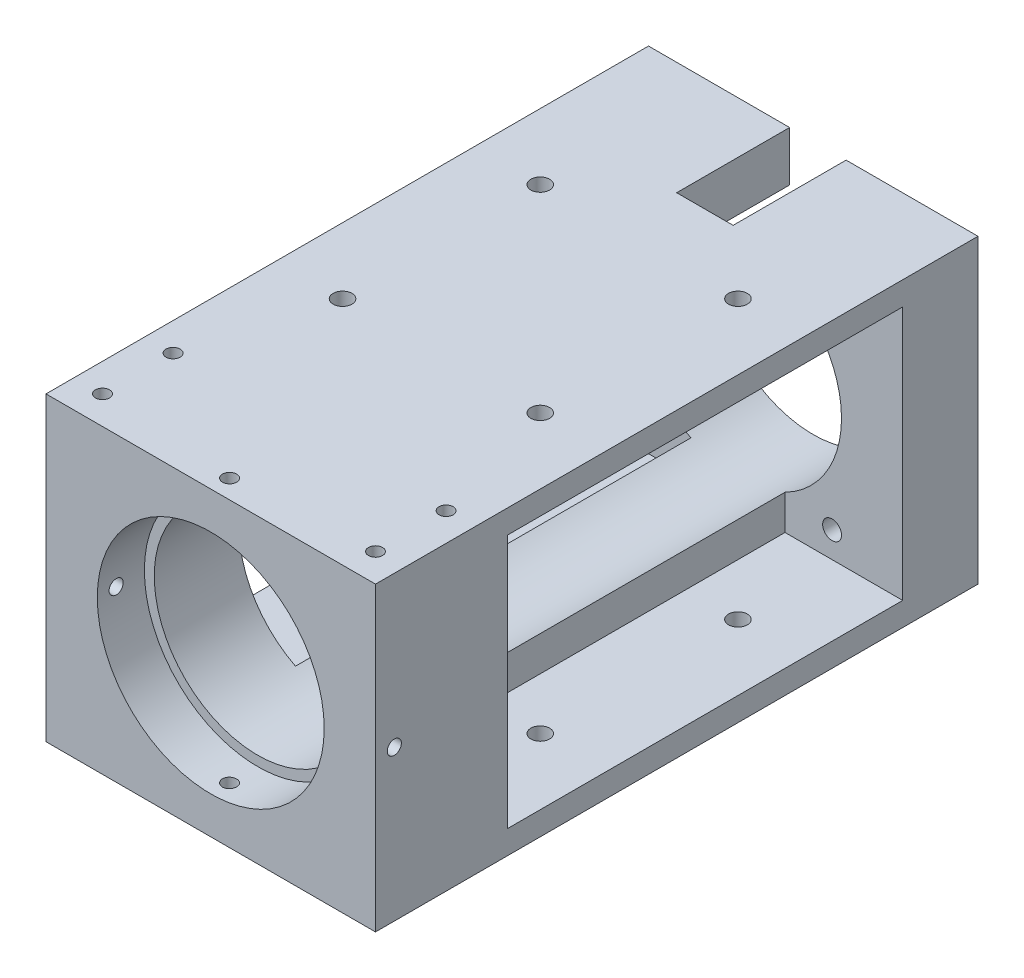
SolidWorks part; units mm, degrees
material "1060 合金"
ref_plane "前视基准面" through (0, 0, 0) normal (0, 0, 1) x (1, 0, 0)
ref_plane "上视基准面" through (0, 0, 0) normal (0, 1, 0) x (1, 0, 0)
ref_plane "右视基准面" through (0, 0, 0) normal (1, 0, 0) x (0, 0, -1)
sketch "草图1" plane through (0, 0, 0) normal (0, 0, 1) x (1, 0, 0)
  line L1 (-35, -32) -> (35, -32)
  line L2 (-35, -32) -> (-35, 32)
  line L3 (-35, 32) -> (35, 32)
  line L4 (35, -32) -> (35, 32)
  line L5 (-35, -32) -> (35, 32) construction
  line L6 (-35, 32) -> (35, -32) construction
  point P0 (0, 0)
  dimension "D1" = 70
  dimension "D2" = 64
extrude "凸台-拉伸1" add sketch "草图1" along normal mid plane 140
sketch "草图2" plane through (0, 0, 70) normal (0, 0, 1) x (1, 0, 0)
  circle A0 centre (0, 0) radius 24.1
  dimension "D1" = 48.2
extrude "切除-拉伸1" cut sketch "草图2" against normal blind 10
sketch "草图3" plane through (0, 32, 0) normal (0, 1, 0) x (1, 0, 0)
  line L0 (35, -70) -> (-35, -70) construction
  circle A0 centre (0, -66) radius 1.5
  point P5 (0, -70)
  dimension "D1" = 3
  dimension "D2" = 4
extrude "切除-拉伸2" cut sketch "草图3" against normal through all
sketch "草图4" plane through (35, 0, 0) normal (1, 0, 0) x (0, 0, -1)
  line L0 (-70, -32) -> (-70, 32) construction
  circle A0 centre (-66, 0) radius 1.5
  dimension "D1" = 3
  dimension "D2" = 4
extrude "切除-拉伸3" cut sketch "草图4" against normal through all
sketch "草图5" plane through (0, 0, 60) normal (0, 0, 1) x (1, 0, 0)
  circle A0 centre (0, 0) radius 22
  dimension "D1" = 44
extrude "切除-拉伸4" cut sketch "草图5" against normal through all
sketch "草图6" plane through (35, 0, 0) normal (1, 0, 0) x (0, 0, -1)
  line L1 (-42, -27) -> (42, -27)
  line L2 (-42, -27) -> (-42, 27)
  line L3 (-42, 27) -> (42, 27)
  line L4 (42, -27) -> (42, 27)
  line L5 (-42, -27) -> (42, 27) construction
  line L6 (-42, 27) -> (42, -27) construction
  point P0 (0, 0)
  dimension "D1" = 54
  dimension "D2" = 84
extrude "切除-拉伸5" cut sketch "草图6" against normal blind 25
mirror "镜向4" about plane through (0, 0, 0) normal (1, 0, 0) of "切除-拉伸5"
sketch "草图7" plane through (0, 32, 0) normal (0, 1, 0) x (1, 0, 0)
  line L0 (-21, 21) -> (21, 21) construction
  circle A0 centre (-21, 21) radius 2
  circle A1 centre (21, 21) radius 2
  point P4 (0, 21)
  dimension "D1" = 4
  dimension "D2" = 42
  dimension "D3" = 21
extrude "切除-拉伸6" cut sketch "草图7" against normal blind 20
sketch "草图8" plane through (0, 27, 0) normal (0, -1, 0) x (1, 0, 0)
  circle A1 centre (21, -21) radius 2 construction
  circle A2 centre (21, -21) radius 5.5
  circle A3 centre (21, -21) radius 5.5
  circle A4 centre (21, -21) radius 2
  circle M2 centre (21, -21) radius 2
  dimension "D1" = 3.5
extrude "切除-拉伸7" [suppressed] cut sketch "草图8" against normal blind 7 contours A3 M2
mirror "镜向1" [suppressed] about plane through (0, 0, 0) normal (1, 0, 0)
mirror "镜向2" about plane through (0, 0, 0) normal (0, 0, 1) of "镜向1", "切除-拉伸7", "切除-拉伸6"
sketch "草图9" plane through (0, 0, 0) normal (1, 0, 0) x (0, 0, -1)
  line L0 (-112.2479, 0) -> (108.0194, 0)
sketch "草图10" plane through (0, 0, -70) normal (0, 0, -1) x (-1, 0, 0)
  circle A0 centre (0, 0) radius 22 construction
  point P0 (0, -22)
sketch "草图11" plane through (0, 32, 0) normal (0, 1, 0) x (1, 0, 0)
  line L0 (-29, -64) -> (29, -64) construction
  line L1 (35, -70) -> (-35, -70) construction
  line L2 (-29, -49) -> (29, -49) construction
  circle A0 centre (-29, -64) radius 1.5
  circle A1 centre (29, -64) radius 1.5
  circle A2 centre (-29, -49) radius 1.5
  circle A3 centre (29, -49) radius 1.5
  point P4 (0, -64)
  point P7 (0, -70)
  point P12 (0, -49)
  dimension "D3" = 3
  dimension "D1" = 58
  dimension "D2" = 6
  dimension "D4" = 15
extrude "切除-拉伸8" cut sketch "草图11" against normal blind 10
sketch "草图12" plane through (35, 0, 0) normal (1, 0, 0) x (0, 0, -1)
  line L0 (-70, -32) -> (70, -32) construction
  line L1 (58, -32) -> (70, -32)
  line L2 (58, -32) -> (58, 32)
  line L3 (58, 32) -> (70, 32)
  line L4 (70, -32) -> (70, 32)
  line L5 (58, -32) -> (70, 32) construction
  line L6 (58, 32) -> (70, -32) construction
  point P0 (64, 0)
  point P6 (64, -32)
  dimension "D2" = 12
extrude "切除-拉伸9" cut sketch "草图12" against normal through all
sketch "草图13" plane through (0, 0, -58) normal (0, 0, -1) x (-1, 0, 0)
  line L0 (35, 32) -> (35, -32) construction
  line L1 (-35, -25) -> (35, -25)
  line L2 (-35, -25) -> (-35, 25)
  line L3 (-35, 25) -> (35, 25)
  line L4 (35, -25) -> (35, 25)
  line L5 (-35, -25) -> (35, 25) construction
  line L6 (-35, 25) -> (35, -25) construction
  circle A0 centre (0, 0) radius 22 construction
  circle A1 centre (0, 0) radius 22
  point P0 (0, 0)
  dimension "D1" = 50
extrude "凸台-拉伸2" add sketch "草图13" along normal blind 68
sketch "草图14" plane through (0, 25, 0) normal (0, 1, 0) x (1, 0, 0)
  line L0 (-35, 58) -> (35, 58) construction
  line L1 (20, 126) -> (-20, 126)
  line L2 (20, 126) -> (20, 58)
  line L3 (20, 58) -> (-20, 58)
  line L4 (-20, 126) -> (-20, 58)
  line L5 (20, 126) -> (-20, 58) construction
  line L6 (20, 58) -> (-20, 126) construction
  line L7 (-35, 126) -> (35, 126) construction
  point P0 (0, 92)
  point P7 (0, 126)
  point P12 (0, 58)
  dimension "D1" = 40
extrude "切除-拉伸10" cut sketch "草图14" against normal blind 20
fillet "圆角1" radius 3 2 edges at (-20, 9.1652, -92) (20, 9.1652, -92)
sketch "草图15" plane through (0, 25, 0) normal (0, 1, 0) x (1, 0, 0)
  line L0 (-30, 68) -> (-30, 116) construction
  line L1 (-35, 126) -> (-35, 58) construction
  line L2 (-35, 126) -> (-20, 126) construction
  circle A0 centre (-30, 68) radius 2
  circle A1 centre (-30, 116) radius 2
  dimension "D1" = 4
  dimension "D2" = 48
  dimension "D3" = 5
  dimension "D4" = 10
extrude "切除-拉伸11" cut sketch "草图15" against normal blind 10 contours A1 | A0 region at (-30, 25, -116)
mirror "镜向3" about plane through (0, 0, 0) normal (0, 1, 0) of "镜向1", "切除-拉伸7", "切除-拉伸6", "镜向2"
sketch "草图16" plane through (0, -32, 0) normal (0, -1, 0) x (1, 0, 0)
  line L0 (27, -48) -> (-27, -48) construction
  line L1 (-27, -48) -> (-27, 62) construction
  line L2 (-27, 62) -> (27, 62) construction
  line L3 (27, 62) -> (27, -48) construction
  line L4 (-35, 70) -> (35, 70) construction
  circle A0 centre (27, 62) radius 2
  circle A1 centre (-27, 62) radius 2
  circle A2 centre (27, -48) radius 2
  circle A3 centre (-27, -48) radius 2
  point P8 (0, 62)
  point P11 (0, 70)
  dimension "D1" = 4
  dimension "D2" = 110
  dimension "D3" = 54
  dimension "D4" = 8
extrude "切除-拉伸12" cut sketch "草图16" against normal blind 8
sketch "草图18" plane through (0, 0, -126) normal (0, 0, -1) x (-1, 0, 0)
  line L7 (20, 25) -> (20, 9.798)
  line L8 (-20, 9.798) -> (-20, 25)
  line L9 (-20, 25) -> (-35, 25)
  line L10 (-35, 25) -> (-35, -25)
  line L11 (-35, -25) -> (35, -25)
  line L12 (35, -25) -> (35, 25)
  line L13 (35, 25) -> (20, 25)
  line L14 (20, 25) -> (20, 9.798)
  line L15 (-20, 9.798) -> (-20, 25)
  line L16 (-20, 25) -> (-35, 25)
  line L17 (-35, 25) -> (-35, -25)
  line L18 (-35, -25) -> (35, -25)
  line L19 (35, -25) -> (35, 25)
  line L20 (35, 25) -> (20, 25)
  arc A3 (20, 9.798) -> (20.24, 8.6222) centre (23, 9.798) ccw
  arc A4 (-20.24, 8.6222) -> (20.24, 8.6222) centre (0, 0) ccw
  arc A5 (-20.24, 8.6222) -> (-20, 9.798) centre (-23, 9.798) ccw
  arc A6 (20, 9.798) -> (20.24, 8.6222) centre (23, 9.798) ccw
  arc A7 (-20.24, 8.6222) -> (20.24, 8.6222) centre (0, 0) ccw
  arc A8 (-20.24, 8.6222) -> (-20, 9.798) centre (-23, 9.798) ccw
  dimension "D1" = 0
extrude "切除-拉伸13" cut sketch "草图18" against normal up to surface (68 mm away) up to face at (0, 21.4194, -58)
sketch "草图19" plane through (0, 0, -58) normal (0, 0, -1) x (-1, 0, 0)
  circle A0 centre (-20, -21.5) radius 2 construction
  circle A1 centre (-20, 21.5) radius 2 construction
  circle A2 centre (20, -21.5) radius 2 construction
  circle A3 centre (20, 21.5) radius 2 construction
  circle A4 centre (-20, -21.5) radius 2
  circle A5 centre (-20, 21.5) radius 2
  circle A6 centre (20, -21.5) radius 2
  circle A7 centre (20, 21.5) radius 2
extrude "切除-拉伸14" cut sketch "草图19" against normal blind 20
sketch "草图20" plane through (0, 32, 0) normal (0, 1, 0) x (1, 0, 0)
  line L0 (-35, 58) -> (35, 58) construction
  line L1 (-5.0201, 58) -> (6.9799, 58)
  line L2 (-5.0201, 58) -> (-5.0201, 34)
  line L3 (-5.0201, 34) -> (6.9799, 34)
  line L4 (6.9799, 58) -> (6.9799, 34)
  point P6 (-5.0201, 58)
  dimension "D1" = 12
  dimension "D2" = 24
extrude "切除-拉伸15" cut sketch "草图20" against normal blind 20
